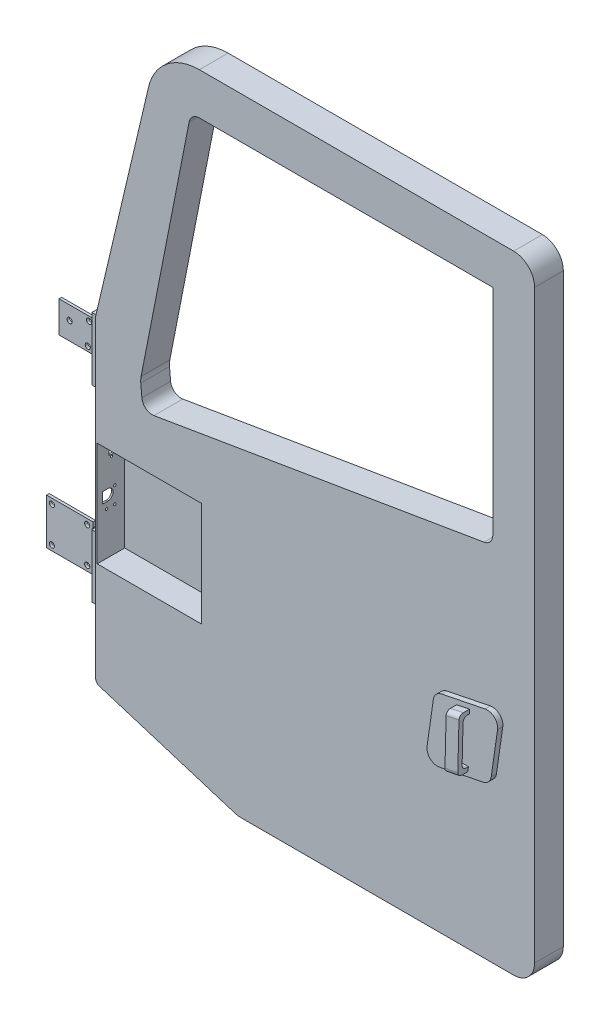
SolidWorks part; units mm, degrees
ref_plane "Front Plane" through (0, 0, 0) normal (0, 0, 1) x (1, 0, 0)
ref_plane "Top Plane" through (0, 0, 0) normal (0, 1, 0) x (1, 0, 0)
ref_plane "Right Plane" through (0, 0, 0) normal (1, 0, 0) x (0, 0, -1)
sketch "Sketch2" plane through (0, 0, 0) normal (0, 0, 1) x (1, 0, 0)
  line L1 (-179.7693, -762.022) -> (482.6, -762.022)
  line L3 (-281.2299, 761.978) -> (482.6, 761.978)
  line L4 (533.4, -711.222) -> (533.4, 711.178)
  line L5 (-459.8603, -656.939) -> (-452.0517, -645.784) construction
  line L6 (-417.9715, 597.0829) -> (44.2876, -63.266) construction
  line L8 (-524.4721, -657.2008) -> (-194.8579, -759.7295)
  line L9 (-306.1723, 639.7777) -> (-423.0219, 45.4039)
  line L10 (-423.7768, 31.1096) -> (-421.1458, 1.4921)
  line L14 (-281.2299, 660.378) -> (431.8, 660.378)
  line L16 (431.7996, 138.4174) -> (431.8, 660.378)
  line L17 (431.8, -660.422) -> (431.8, 660.378) construction
  line L18 (-172.0509, -660.422) -> (431.8, -660.422) construction
  line L19 (-533.4, 116.926) -> (-405.8883, 659.253)
  line L20 (-367.7549, -599.547) -> (-172.0509, -660.422) construction
  line L21 (-55.7209, -79.6007) -> (521.0599, 744.3665) construction
  line L22 (-306.1723, 639.7777) -> (-424.4164, 38.3105) construction
  line L23 (-424.4164, 38.3105) -> (-367.7549, -599.547) construction
  line L24 (-414.3579, -691.4526) -> (-194.8579, -759.7295) construction
  line L25 (-179.7693, -762.022) -> (482.6, -762.022)
  line L27 (-281.2299, 761.978) -> (482.6, 761.978)
  line L28 (533.4, -711.222) -> (533.4, 711.178)
  line L29 (-459.8603, -656.939) -> (-452.0517, -645.784) construction
  line L30 (-417.9715, 597.0829) -> (44.2876, -63.266) construction
  line L31 (-533.4, 116.926) -> (-466.2749, -638.723) construction
  line L32 (-391.6402, -21.3099) -> (410.6048, 113.3679)
  line L33 (-55.7209, -79.6007) -> (521.0599, 744.3665) construction
  line L34 (-281.2299, 761.978) -> (482.6, 761.978)
  line L35 (-533.4, 116.926) -> (-533.4, -645.074)
  line L36 (-179.7693, -762.022) -> (482.6, -762.022)
  line L37 (533.4, 711.178) -> (533.4, -711.222)
  line L38 (-417.9715, 597.0829) -> (44.2876, -63.266) construction
  line L39 (-471.5639, -673.6583) -> (-452.0517, -645.784) construction
  line L40 (-405.8883, 659.253) -> (-528.8132, 33.9764) construction
  line L41 (-55.7209, -79.6007) -> (521.0599, 744.3665) construction
  arc A0 (-405.8883, 659.253) -> (-281.2299, 761.978) centre (-281.2299, 634.978) cw
  arc A3 (533.4, 711.178) -> (482.6, 761.978) centre (482.6, 711.178) ccw
  arc A4 (482.6, -762.022) -> (533.4, -711.222) centre (482.6, -711.222) ccw
  arc A5 (-194.8579, -759.7295) -> (-179.7693, -762.022) centre (-179.7693, -711.222) ccw
  arc A7 (-367.7549, -599.547) -> (-367.7549, -599.547) centre (-367.7549, -599.547) ccw
  arc A8 (-172.0509, -660.422) -> (-172.0509, -660.422) centre (-172.0509, -660.422) ccw
  arc A9 (431.8, -660.422) -> (431.8, -660.422) centre (431.8, -660.422) ccw
  arc A10 (431.8, 660.378) -> (431.8, 660.378) centre (431.8, 660.378) ccw
  arc A11 (-306.1723, 639.7777) -> (-281.2299, 660.378) centre (-281.2299, 634.978) cw
  arc A12 (-423.0219, 45.4039) -> (-423.7768, 31.1096) centre (-373.176, 35.6045) ccw
  arc A13 (-424.4164, 38.3105) -> (-424.4164, 38.3105) centre (-424.4164, 38.3105) ccw construction
  arc A16 (-466.2749, -638.723) -> (-414.3579, -691.4526) centre (-391.0208, -616.5518) ccw construction
  arc A17 (-533.4, -645.074) -> (-524.4721, -657.2008) centre (-520.7, -645.074) ccw
  arc A18 (-528.8132, 33.9764) -> (-533.4, 116.926) centre (-501.9071, 77.0658) ccw construction
  arc A19 (431.7996, 138.4174) -> (410.6048, 113.3679) centre (406.3996, 138.4174) cw
  arc A20 (-391.6402, -21.3099) -> (-421.1458, 1.4921) centre (-395.8454, 3.7395) cw
  point P0 (0, 0)
  point P16 (-533.4, -0.0244)
  point P56 (0, 0)
  point P61 (0, 0)
  dimension "D3" = 127
  dimension "D6" = 50.8
  dimension "D8" = 50.8
  dimension "D2" = 12.7
  dimension "D9" = 25.4
  dimension "D1" = 1066.8
  dimension "D4" = 1524
  dimension "D5" = 762
  dimension "D7" = 101.6
extrude "Boss-Extrude1" add sketch "Sketch2" along normal mid plane 69.85 contours L8 A5 L1 A4 L4 A3 L3 A0 L10 A12 L9 A11 L14 L16 A20 region at (22.1716, -171.0663, 0)
ref_plane "bottom" through (0, -762.022, 0) normal (0, -1, 0) x (-1, 0, 0)
ref_plane "top door check" through (0, -158.772, 0) normal (0, -1, 0) x (-1, 0, 0)
ref_plane "door check mid" through (0, -176.2345, 0) normal (0, -1, 0) x (-1, 0, 0)
ref_plane "bottom door check" through (0, -193.697, 0) normal (0, -1, 0) x (-1, 0, 0)
ref_plane "top hinge top hole" through (0, 66.653, 0) normal (0, -1, 0) x (-1, 0, 0)
ref_plane "top hinge middle hole" through (0, 44.428, 0) normal (0, -1, 0) x (-1, 0, 0)
ref_plane "top hinge bottom hole" through (0, 12.678, 0) normal (0, -1, 0) x (-1, 0, 0)
ref_plane "bottome hinge top hole" through (0, -363.5595, 0) normal (0, -1, 0) x (-1, 0, 0)
ref_plane "bottom hinge bottom hole" through (0, -449.2845, 0) normal (0, -1, 0) x (-1, 0, 0)
ref_plane "Plane1" through (0, 0, 31.75) normal (0, 0, 1) x (1, 0, 0)
sketch "Sketch3" plane through (0, 0, 34.925) normal (0, 0, 1) x (1, 0, 0)
  line L0 (320.1959, -245.101) -> (425.9265, -223.6716)
  line L3 (314.9201, -401.6691) -> (420.6507, -380.2397)
  line L4 (456.113, -252.1835) -> (440.7462, -358.9639)
  line L5 (300.1004, -266.3768) -> (284.7336, -373.1572)
  line L6 (310.4001, -194.8067) -> (287.3499, -354.9772) construction
  line L7 (-487.6326, -408.8312) -> (533.4008, -201.8888) construction
  line L8 (-457.3598, -558.1943) -> (563.6737, -351.2518) construction
  line L9 (461.2461, -216.515) -> (438.1959, -376.6855) construction
  line L10 (373.0612, -234.3863) -> (367.7854, -390.9544) construction
  line L11 (360.2667, -236.9795) -> (354.9908, -393.5476)
  line L12 (385.8558, -231.7931) -> (380.58, -388.3612)
  line L13 (360.3684, -233.9586) -> (355.0926, -390.5267) construction
  line L14 (385.754, -234.814) -> (380.4782, -391.3821) construction
  arc A0 (300.1004, -266.3768) -> (320.1959, -245.101) centre (325.2414, -269.9949) cw
  arc A1 (284.7336, -373.1572) -> (314.9201, -401.6691) centre (309.8746, -376.7752) ccw
  arc A2 (440.7462, -358.9639) -> (420.6507, -380.2397) centre (415.6052, -355.3458) cw
  arc A3 (456.113, -252.1835) -> (425.9265, -223.6716) centre (430.972, -248.5655) ccw
  dimension "D3" = 25.4
  dimension "D1" = 152.4
  dimension "D2" = 152.4
  dimension "D4" = 12.7
  dimension "D5" = 12.7
extrude "Boss-Extrude2" add sketch "Sketch3" along normal blind 12.7 contours L5 A1 L3 L11 L0 A0 | L4 A3 L0 L12 L3 A2 | L12 L0 L11 L3 region at (325.2101, -323.7797, 34.925) region at (370.4233, -312.6704, 34.925) region at (415.6365, -301.561, 34.925)
sketch "Sketch5" plane through (0, 0, 34.925) normal (0, 0, 1) x (1, 0, 0)
  line L6 (-179.7693, -762.022) -> (482.6, -762.022)
  line L12 (-179.7693, -762.022) -> (482.6, -762.022)
  line L28 (387.9598, -243.0291) -> (384.7172, -375.8602)
  line L29 (353.4927, -382.1888) -> (356.7353, -249.3577)
  line L30 (387.9598, -243.0291) -> (356.7353, -249.3577)
  line L31 (384.7172, -375.8602) -> (353.4927, -382.1888)
  line L32 (320.1959, -245.101) -> (425.9265, -223.6716) construction
  line L33 (314.9201, -401.6691) -> (420.6507, -380.2397) construction
  line L34 (320.1959, -245.101) -> (425.9265, -223.6716) construction
  line L35 (314.9201, -401.6691) -> (420.6507, -380.2397) construction
  dimension "D2" = 11.43
  dimension "D3" = 11.43
  dimension "D1" = 0
extrude "Boss-Extrude4" add sketch "Sketch5" along normal blind 38.1 contours L31 L28 L30 L29 region at (370.7262, -312.609, 34.925)
sketch "Sketch6" plane through (393.6581, -9.61, 0) normal (0.9997, -0.0244, 0) x (0, 0, -1)
  line L9 (-47.625, -356.1994) -> (-62.865, -356.1994)
  line L10 (-62.865, -356.1994) -> (-62.865, -243.6487)
  line L11 (-62.865, -243.6487) -> (-47.625, -243.6487)
  line L12 (-47.625, -356.1994) -> (-62.865, -356.1994)
  line L13 (-62.865, -356.1994) -> (-62.865, -243.6487)
  line L14 (-62.865, -243.6487) -> (-47.625, -243.6487)
  line M5 (-47.625, -366.3594) -> (-47.625, -233.4887)
  dimension "D1" = 10.16
extrude "Cut-Extrude6" cut sketch "Sketch6" against normal through all and the other way through all contours L14 L13 L12 M5 region at (386.3385, -309.4447, 55.245)
fillet "Fillet5" radius 10.16 4 edges at (369.1049, -379.0245, 73.025) (369.4394, -365.3242, 62.865) (372.1861, -252.8071, 62.865) (372.3476, -246.1934, 73.025)
sketch "Sketch7" plane through (-533.4, 59.3738, 0) normal (1, 0, 0) x (0, 0, 1)
  line L0 (0, 821.3958) -> (0, -702.6042) construction
  line L1 (34.925, 821.3958) -> (-34.925, 821.3958) construction
  line L2 (34.925, -702.6042) -> (-34.925, -702.6042) construction
  line L4 (-31.75, -57.5522) -> (31.75, -57.5522)
  line L5 (-31.75, -57.5522) -> (-31.75, 94.8478)
  line L6 (-31.75, 94.8478) -> (31.75, 94.8478)
  line L11 (31.75, -57.5522) -> (31.75, 94.8478)
  line L12 (-31.75, -57.5522) -> (31.75, 94.8478) construction
  line L13 (-31.75, 94.8478) -> (31.75, -57.5522) construction
  line L19 (34.925, -57.5522) -> (-34.925, -57.5522) construction
  line L21 (-31.75, 552.0478) -> (31.75, 552.0478)
  line L28 (-31.75, 552.0478) -> (-31.75, 399.6478)
  line L29 (-31.75, 399.6478) -> (31.75, 399.6478)
  line L30 (31.75, 552.0478) -> (31.75, 399.6478)
  line L31 (-31.75, 552.0478) -> (31.75, 399.6478) construction
  line L32 (-31.75, 399.6478) -> (31.75, 552.0478) construction
  point P6 (0, 18.6478)
  point P13 (0, 475.8478)
  dimension "D1" = 63.5
  dimension "D2" = 152.4
  dimension "D4" = 304.8
extrude "Boss-Extrude5" add sketch "Sketch7" against normal blind 12.7
sketch "Sketch16" plane through (0, 0, 34.925) normal (0, 0, 1) x (1, 0, 0)
  line L1 (-529.59, -148.3099) -> (-529.59, -402.3099)
  line L3 (-275.59, -402.3099) -> (-275.59, -148.3099)
  line L5 (-533.4, 116.926) -> (-533.4, -645.074) construction
  line L6 (-529.59, -148.3099) -> (-275.59, -148.3099)
  line L7 (-529.59, -402.3099) -> (-275.59, -402.3099)
  dimension "D1" = 254
  dimension "D2" = 127
  dimension "D3" = 254
  dimension "D4" = 3.81
extrude "Cut-Extrude8" cut sketch "Sketch16" against normal blind 66.675
sketch "Sketch20" plane through (-533.4, 0, 0) normal (-1, 0, 0) x (0, 0, 1)
  line L0 (-38.4175, -176.2345) -> (38.4175, -176.2345) construction
  line L1 (-6.35, -188.9345) -> (6.35, -188.9345)
  line L2 (-6.35, -188.9345) -> (-6.35, -163.5345)
  line L3 (-6.35, -163.5345) -> (6.35, -163.5345)
  line L4 (6.35, -188.9345) -> (6.35, -163.5345)
  line L5 (-6.35, -188.9345) -> (6.35, -163.5345) construction
  line L6 (-6.35, -163.5345) -> (6.35, -188.9345) construction
  line L7 (-38.4175, -158.772) -> (38.4175, -158.772) construction
  line L8 (6.35, -176.2345) -> (-6.35, -176.2345) construction
  circle A0 centre (0, -158.772) radius 2.54
  circle A1 centre (0, -193.697) radius 2.54
  point P0 (0, -176.2345)
  dimension "D3" = 5.08
  dimension "D1" = 12.7
  dimension "D2" = 25.4
extrude "Cut-Extrude12" cut sketch "Sketch20" against normal up to surface (3.81 mm away) contours A0 | L4 L3 L2 L1 | A1 up to face at (-529.59, -275.3099, 1.5875)
sketch "Sketch21" plane through (0, 0, 0) normal (0, 0, 1) x (1, 0, 0)
  line L0 (-38.4175, 66.653) -> (38.4175, 66.653) construction
  line L1 (-202.423, 66.653) -> (-1027.3811, 66.653) construction
  line L2 (-212.5576, 44.428) -> (-1027.3811, 44.428) construction
  line L3 (-38.4175, 44.428) -> (38.4175, 44.428) construction
  line L4 (-212.5576, 12.678) -> (-1027.3811, 12.678) construction
  line L5 (-38.4175, 12.678) -> (38.4175, 12.678) construction
  line L6 (-546.1, 116.926) -> (-546.1, -35.474) construction
  line L7 (-558.8, 66.653) -> (-546.1, 66.653)
  line L8 (-558.8, 66.653) -> (-558.8, 12.678)
  line L9 (-558.8, 12.678) -> (-546.1, 12.678)
  line L10 (-546.1, 66.653) -> (-546.1, 12.678)
  line L11 (-654.05, 77.448) -> (-654.05, 1.248)
  line L12 (-654.05, 77.448) -> (-558.8, 77.448)
  line L15 (-558.8, 77.448) -> (-558.8, 12.678)
  line L16 (-654.05, 77.448) -> (-558.8, 12.678) construction
  line L17 (-654.05, 10.0872) -> (-558.8, 77.448) construction
  line L18 (-654.05, 1.248) -> (-558.8, 1.248)
  line L19 (-558.8, 12.678) -> (-558.8, 1.248)
  circle A0 centre (-584.2, 12.678) radius 6.35
  circle A1 centre (-628.65, 44.428) radius 6.35
  circle A2 centre (-581.025, 66.653) radius 6.35
  point P18 (-605.4912, 44.428)
  dimension "D2" = 12.7
  dimension "D3" = 25.4
  dimension "D4" = 69.85
  dimension "D5" = 22.225
  dimension "D6" = 95.25
  dimension "D9" = 64.77
  dimension "D1" = 12.7
  dimension "D7" = 76.2
  dimension "D8" = 33.02
extrude "Boss-Extrude8" add sketch "Sketch21" along normal mid plane 6.35 contours L19 L8 L15 L12 L11 L18 A2 A1 A0 | L10 L7 L8 L9 region at (-552.45, 39.6655, 0) region at (-606.8928, 39.2427, 0)
sketch "Sketch26" plane through (0, 0, 0) normal (0, 0, 1) x (1, 0, 0)
  line L0 (-193.6896, -363.5595) -> (-881.8717, -363.5595) construction
  line L1 (-38.4175, -363.5595) -> (38.4175, -363.5595) construction
  line L2 (-133.4597, -449.2845) -> (-881.8717, -449.2845) construction
  line L3 (-38.4175, -449.2845) -> (38.4175, -449.2845) construction
  line L4 (-625.8948, -363.5595) -> (-625.8948, -449.2845) construction
  line L5 (-625.8948, -406.422) -> (-892.4677, -406.422) construction
  line L6 (-546.1, -340.274) -> (-546.1, -492.674) construction
  line L7 (-571.5, -449.2845) -> (-546.1, -449.2845)
  line L8 (-571.5, -449.2845) -> (-571.5, -363.5595)
  line L9 (-571.5, -363.5595) -> (-546.1, -363.5595)
  line L10 (-546.1, -449.2845) -> (-546.1, -363.5595)
  line L11 (-571.5, -449.2845) -> (-546.1, -363.5595) construction
  line L12 (-571.5, -363.5595) -> (-546.1, -449.2845) construction
  point P12 (-558.8, -406.422)
  dimension "D1" = 25.4
extrude "Boss-Extrude12" add sketch "Sketch26" along normal mid plane 12.7
sketch "Sketch27" plane through (0, 0, 0) normal (0, 0, 1) x (1, 0, 0)
  line L0 (-211.2814, -363.5595) -> (-919.4505, -363.5595) construction
  line L1 (-38.4175, -363.5595) -> (38.4175, -363.5595) construction
  line L2 (-201.3631, -449.2845) -> (-928.7076, -449.2845) construction
  line L3 (-38.4175, -449.2845) -> (38.4175, -449.2845) construction
  line L4 (-571.5, -363.5595) -> (-571.5, -449.2845) construction
  line L5 (-631.7994, -363.5595) -> (-631.7994, -449.2845) construction
  line L6 (-631.7994, -406.422) -> (-919.4505, -406.422) construction
  line L8 (-684.2125, -461.9845) -> (-571.5, -461.9845)
  line L9 (-684.2125, -461.9845) -> (-684.2125, -350.8595)
  line L10 (-684.2125, -350.8595) -> (-571.5, -350.8595)
  line L11 (-571.5, -461.9845) -> (-571.5, -350.8595)
  line L12 (-684.2125, -461.9845) -> (-571.5, -350.8595) construction
  line L13 (-684.2125, -350.8595) -> (-571.5, -461.9845) construction
  circle A0 centre (-585.7875, -363.5595) radius 6.35
  circle A2 centre (-671.5125, -449.2845) radius 6.35
  circle A4 centre (-585.7875, -449.2845) radius 6.35
  circle A5 centre (-671.5125, -363.5595) radius 6.35
  point P22 (-627.8563, -406.422)
  dimension "D1" = 12.7
  dimension "D2" = 100.0125
  dimension "D3" = 14.2875
  dimension "D4" = 12.7
extrude "Boss-Extrude13" add sketch "Sketch27" along normal mid plane 6.35
sketch "Sketch28" plane through (-533.4, 0, 0) normal (-1, 0, 0) x (0, 0, 1)
  line L1 (9.225, -256.897) -> (22.225, -256.897)
  line L3 (9.225, -282.897) -> (22.225, -282.897)
  line L4 (22.225, -256.897) -> (22.225, -282.897)
  line L5 (34.925, -245.101) -> (34.925, -223.6716) construction
  line L6 (-38.4175, -193.697) -> (38.4175, -193.697) construction
  arc A6 (9.225, -256.897) -> (9.225, -282.897) centre (9.225, -269.897) ccw
  circle A7 centre (-7.705, -258.147) radius 3
  circle A8 centre (-7.705, -298.147) radius 3
  circle A9 centre (12.295, -298.147) radius 3
  point P7 (-3.775, -269.897)
  point P16 (22.225, -269.897)
  dimension "D4" = 40
  dimension "D5" = 26
  dimension "D6" = 26
  dimension "D1" = 11.75
  dimension "D2" = 3.93
  dimension "D3" = 20
  dimension "D8" = 12.7
  dimension "D7" = 6
  dimension "D9" = 13
  dimension "D10" = 76.2
extrude "Cut-Extrude13" cut sketch "Sketch28" against normal up to surface (3.81 mm away) contours L1 A6 L3 L4 | A8 | A9 | A7 region at (-533.4, -269.897, 10.4385) region at (-533.4, -298.147, -7.705) region at (-533.4, -298.147, 12.295) up to face at (-529.59, -176.2345, 0)
equation "\"doorwidth\"= 42in"
equation "\"D1@Sketch2\"=\"doorwidth\""
equation "\"doorheight\"= 60in"
equation "\"D4@Sketch2\"=\"doorheight\""
equation "\"doorthickness\"= 2.75in"
equation "\"D1@Boss-Extrude1\"=\"doorthickness\""
equation "\"hingewidth\"= 2.5in"
equation "\"hingeheight\"= 6in"
equation "\"distanceofhinges\"= 12in"
equation "\"D1@Sketch7\"=\"hingewidth\""
equation "\"D2@Sketch7\"=\"hingeheight\""
equation "\"D4@Sketch7\"=\"distanceofhinges\""
